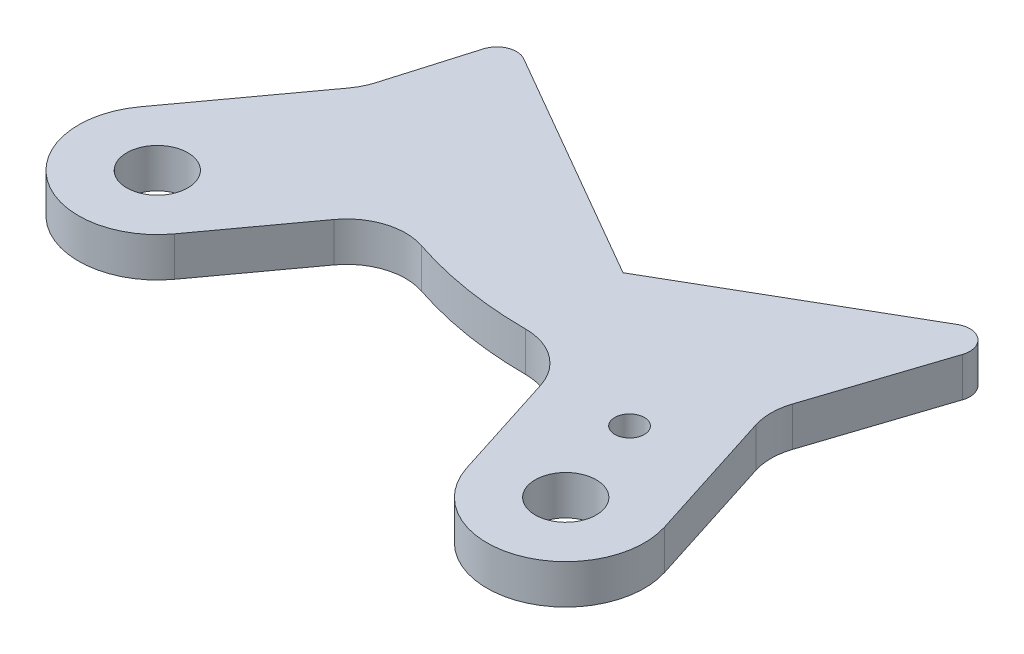
SolidWorks part; units mm, degrees
ref_plane "前视基准面" through (0, 0, 0) normal (0, 0, 1) x (1, 0, 0)
ref_plane "上视基准面" through (0, 0, 0) normal (0, 1, 0) x (1, 0, 0)
ref_plane "右视基准面" through (0, 0, 0) normal (1, 0, 0) x (0, 0, -1)
other "Configuration Table"
sketch "草图1" plane through (0, 0, 0) normal (0, 1, 0) x (1, 0, 0)
  line L0 (-9.4276, 12.118) -> (-14.206, 5.5725)
  line L1 (-7.7445, 0.8555) -> (-2.9662, 7.401)
  line L2 (5.3573, 25.5867) -> (-10.9753, 3.214)
  line L3 (9.974, -2.0172) -> (7.5085, 5.7028)
  line L4 (17.5948, 0.4166) -> (15.1293, 8.1366)
  line L5 (13.7844, -0.8003) -> (5.3573, 25.5867)
  line L6 (15.1293, 8.1366) -> (19.5389, 20.5484)
  line L7 (-9.4276, 12.118) -> (-9.6898, 25.2872)
  circle A0 centre (-10.9753, 3.214) radius 1.55
  circle A1 centre (13.7844, -0.8003) radius 1.55
  circle A2 centre (5.3573, 25.5867) radius 15.05
  circle A3 centre (-10.9753, 3.214) radius 4
  circle A4 centre (13.7844, -0.8003) radius 4
  circle A5 centre (5.3573, 25.5867) radius 20
  dimension "D1" = 3.1
  dimension "D2" = 3.1
  dimension "D3" = 30.1
  dimension "D4" = 40
  dimension "D5" = 8
extrude "凸台-拉伸1" add sketch "草图1" along normal blind 2 contours A3 A0 | A5 L2 A3 L1 | A5 L3 A4 L5 | A4 A1 | A5 L5 A4 L4 | A5 L0 A3 L2 | L7 A5 L2 A2 | A5 L5 A2 L2 | L5 A5 L6 A2 region at (-9.5906, 0, -8.8946) region at (-7.3962, 0, -14.5583) region at (-11.5746, 0, -7.0544) region at (-5.9867, 0, -6.2636) region at (2.6367, 0, -8.8063) region at (13.9729, 0, -11.0937) region at (14.2655, 0, -5.0268) region at (17.6249, 0, 0.2019) region at (10.0149, 0, -3.6693)
sketch "草图4" plane through (0, 2, 0) normal (0, 1, 0) x (1, 0, 0)
  line L0 (18.3909, 18.0617) -> (15.1293, 8.1366)
  line L1 (5.3573, 10.5367) -> (18.3909, 18.0617)
  line L2 (18.3909, 18.0617) -> (18.3909, 33.1117)
  line L3 (18.3909, 33.1117) -> (5.3573, 40.6367)
  line L4 (5.3573, 40.6367) -> (-7.6764, 33.1117)
  line L5 (-7.6764, 33.1117) -> (-7.6764, 18.0617)
  line L6 (-7.6764, 18.0617) -> (5.3573, 10.5367)
  line L7 (15.1293, 8.1366) -> (19.5389, 20.5484)
  line L8 (-9.6898, 25.2872) -> (-9.4276, 12.118)
  line L9 (-9.4276, 12.118) -> (-7.6764, 18.0617)
  arc A0 (-9.6898, 25.2872) -> (19.5389, 20.5484) centre (5.3573, 25.5867) ccw construction
  arc A1 (-9.6898, 25.2872) -> (19.5389, 20.5484) centre (5.3573, 25.5867) ccw
  circle A2 centre (5.3573, 25.5867) radius 13.0337 construction
  line M14 (15.1293, 8.1366) -> (19.5389, 20.5484)
  arc M15 (19.5389, 20.5484) -> (-9.6898, 25.2872) centre (5.3573, 25.5867) cw
  line M16 (-9.6898, 25.2872) -> (-9.4276, 12.118)
  dimension "D1" = 15.05
extrude "切除-拉伸2" cut sketch "草图4" against normal through all contours L9 M16 M15 | L0 M15 M14 region at (17.5892, 2, -15.305) region at (-8.9469, 2, -17.7371)
extrude "凸台-拉伸3" add sketch "草图4<3>" against normal up to surface (2 mm away) contours L6 M15 | L1 M15 region at (12.2798, 2, -13.5966) region at (-1.5652, 2, -13.5966) up to face at (2.532, 0, -5.9036)
sketch "草图4<3>" plane through (0, 2, 0) normal (0, 1, 0) x (1, 0, 0) same geometry as "草图4"
fillet "圆角1" radius 3 4 edges at (-9.4276, 1, -12.118) (-2.9662, 1, -7.401) (7.5085, 1, -5.7028) (15.1293, 1, -8.1366)
fillet "圆角2" radius 1 2 edges at (-7.6764, 1, -18.0617) (18.3909, 1, -18.0617)
sketch "草图5" plane through (0, 2, 0) normal (0, 1, 0) x (1, 0, 0)
  line L0 (12.2632, 3.9627) -> (13.7844, -0.8003) construction
  line L1 (17.5948, 0.4166) -> (15.425, 7.2107) construction
  circle A0 centre (12.2632, 3.9627) radius 0.75
  dimension "D1" = 1.5
  dimension "D2" = 5
extrude "切除-拉伸3" cut sketch "草图5" against normal blind 10
